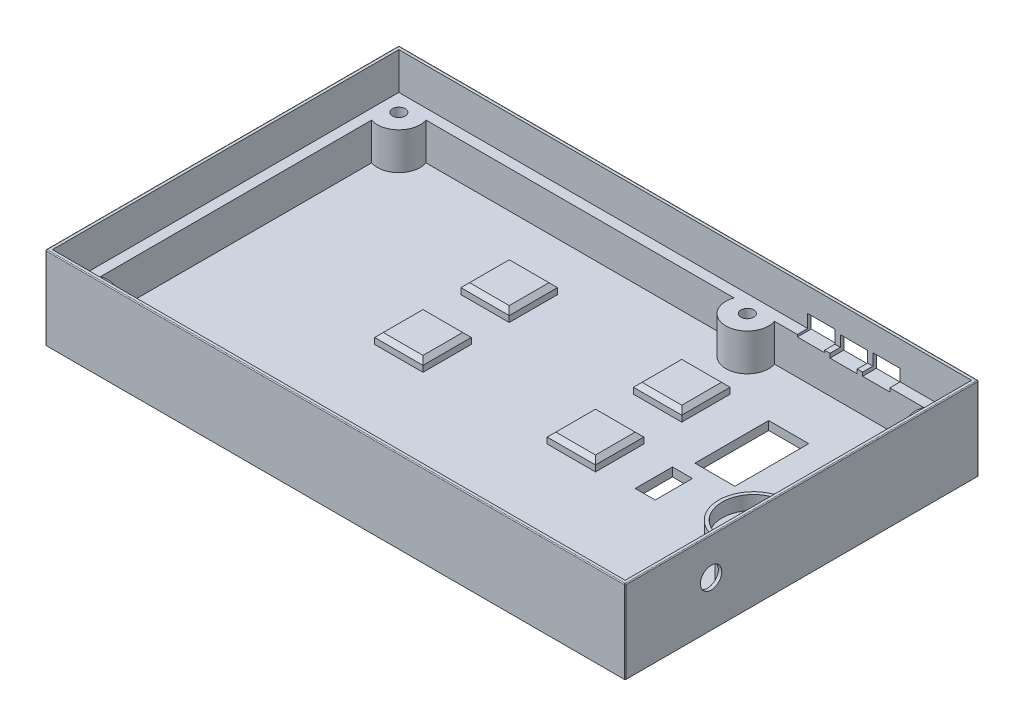
SolidWorks part; units mm, degrees
ref_plane "Front Plane" through (0, 0, 0) normal (0, 0, 1) x (1, 0, 0)
ref_plane "Top Plane" through (0, 0, 0) normal (0, 1, 0) x (1, 0, 0)
ref_plane "Right Plane" through (0, 0, 0) normal (1, 0, 0) x (0, 0, -1)
sketch "BaseSketch1" plane through (0, 0, 0) normal (0, 1, 0) x (1, 0, 0)
  line L1 (0, 0) -> (168, 0)
  line L2 (0, 0) -> (0, 102.4)
  line L3 (0, 102.4) -> (168, 102.4)
  line L4 (168, 0) -> (168, 102.4)
  line L5 (126.2, 83.4) -> (137.8, 83.4)
  line L6 (126.2, 83.4) -> (126.2, 62)
  line L7 (126.2, 62) -> (137.8, 62)
  line L8 (137.8, 83.4) -> (137.8, 62)
  line L9 (123.9, 47) -> (129.7, 47)
  line L10 (123.9, 47) -> (123.9, 57.8)
  line L11 (123.9, 57.8) -> (129.7, 57.8)
  line L12 (129.7, 47) -> (129.7, 57.8)
  circle A0 centre (57, 77.4) radius 2
  circle A1 centre (107, 77.4) radius 2
  circle A2 centre (57, 52.4) radius 2
  circle A3 centre (107, 52.4) radius 2
  circle A4 centre (6, 96.4) radius 1.85
  circle A5 centre (6, 6) radius 1.85
  circle A6 centre (162, 6) radius 1.85
  circle A7 centre (162, 96.4) radius 1.85
  circle A8 centre (107, 96.4) radius 1.85
  dimension "D16" = 3.7
  dimension "D7" = 4
  dimension "D1" = 102.4
  dimension "D2" = 168
  dimension "D3" = 50
  dimension "D4" = 25
  dimension "D6" = 25
  dimension "D8" = 21.4
  dimension "D9" = 11.6
  dimension "D10" = 40.4
  dimension "D12" = 5.8
  dimension "D13" = 10.8
  dimension "D15" = 55.4
  dimension "D17" = 6
  dimension "D18" = 6
  dimension "D19" = 6
  dimension "D20" = 6
  dimension "D5" = 57
  dimension "D11" = 41.8
  dimension "D14" = 44.1
  dimension "D21" = 107
extrude "BaseBoss-Extrude1" add sketch "BaseSketch1" along normal blind 2.5
sketch "Sketch2" plane through (0, 2.5, 0) normal (0, 1, 0) x (1, 0, 0)
  line L1 (0, 0) -> (168, 0)
  line L2 (0, 0) -> (0, 102.4)
  line L3 (0, 102.4) -> (168, 102.4)
  line L4 (168, 0) -> (168, 102.4)
  line L5 (4, 98.4) -> (164, 98.4)
  line L6 (4, 98.4) -> (4, 4)
  line L7 (4, 4) -> (164, 4)
  line L8 (164, 98.4) -> (164, 4)
  dimension "D1" = 4
  dimension "D2" = 4
  dimension "D3" = 4
  dimension "D4" = 4
extrude "WallBoss-Extrude2" add sketch "Sketch2" along normal blind 21.5
sketch "Sketch3" plane through (0, 2.5, 0) normal (0, 1, 0) x (1, 0, 0)
  line L1 (50, 84.4) -> (64, 84.4)
  line L2 (50, 84.4) -> (50, 70.4)
  line L3 (50, 70.4) -> (64, 70.4)
  line L4 (64, 84.4) -> (64, 70.4)
  line L5 (50, 84.4) -> (64, 70.4) construction
  line L6 (50, 70.4) -> (64, 84.4) construction
  line L7 (50, 59.4) -> (64, 59.4)
  line L8 (50, 59.4) -> (50, 45.4)
  line L9 (50, 45.4) -> (64, 45.4)
  line L10 (64, 59.4) -> (64, 45.4)
  line L11 (50, 59.4) -> (64, 45.4) construction
  line L12 (50, 45.4) -> (64, 59.4) construction
  line L13 (100, 84.4) -> (114, 84.4)
  line L14 (100, 84.4) -> (100, 70.4)
  line L15 (100, 70.4) -> (114, 70.4)
  line L16 (114, 84.4) -> (114, 70.4)
  line L17 (100, 84.4) -> (114, 70.4) construction
  line L18 (100, 70.4) -> (114, 84.4) construction
  line L19 (100, 59.4) -> (114, 59.4)
  line L20 (100, 59.4) -> (100, 45.4)
  line L21 (100, 45.4) -> (114, 45.4)
  line L22 (114, 59.4) -> (114, 45.4)
  line L23 (100, 59.4) -> (114, 45.4) construction
  line L24 (100, 45.4) -> (114, 59.4) construction
  point P0 (57, 77.4)
  point P6 (57, 52.4)
  point P12 (107, 77.4)
  point P18 (107, 52.4)
  dimension "D1" = 14
extrude "MountHoleBoss-Extrude3" add sketch "Sketch3" along normal blind 3
chamfer "MountHoleBossChamfer3" distance 1.25 angle 45 16 edges at (57, 5.5, -59.4) (107, 5.5, -59.4) (107, 5.5, -84.4) (57, 5.5, -84.4) (50, 5.5, -52.4) (100, 5.5, -52.4) (100, 5.5, -77.4) (50, 5.5, -77.4) (64, 5.5, -52.4) (114, 5.5, -52.4) (114, 5.5, -77.4) (64, 5.5, -77.4) (57, 5.5, -70.4) (57, 5.5, -45.4) (107, 5.5, -45.4) (107, 5.5, -70.4)
sketch "HDMI7MountHolesSketch8" plane through (0, 2.5, 0) normal (0, 1, 0) x (1, 0, 0)
  line L0 (164, 98.4) -> (4, 98.4) construction
  line L1 (4, 98.4) -> (4, 4) construction
  line L2 (4, 90.5243) -> (4, 98.4)
  line L3 (4, 98.4) -> (11.8757, 98.4)
  line L4 (164, 4) -> (164, 98.4) construction
  line L5 (4, 4) -> (164, 4) construction
  line L6 (4, 98.4) -> (4, 4) construction
  line L7 (4, 4) -> (164, 4) construction
  line L8 (156.1243, 98.4) -> (164, 98.4)
  line L9 (164, 98.4) -> (164, 90.5243)
  line L10 (156.1243, 4) -> (164, 4)
  line L11 (164, 4) -> (164, 11.8757)
  line L12 (11.8757, 4) -> (4, 4)
  line L13 (4, 4) -> (4, 11.8757)
  line L14 (101.1243, 98.4) -> (112.8757, 98.4)
  arc A0 (11.8757, 98.4) -> (4, 90.5243) centre (6, 96.4) cw
  circle A1 centre (6, 96.4) radius 1.85
  circle A2 centre (6, 96.4) radius 1.85 construction
  circle A3 centre (162, 96.4) radius 1.85
  circle A4 centre (162, 96.4) radius 1.85 construction
  arc A5 (164, 90.5243) -> (156.1243, 98.4) centre (162, 96.4) cw
  arc A6 (164, 11.8757) -> (156.1243, 4) centre (162, 6) ccw
  arc A7 (4, 11.8757) -> (11.8757, 4) centre (6, 6) cw
  circle A8 centre (162, 6) radius 1.85
  circle A9 centre (162, 6) radius 1.85 construction
  circle A10 centre (6, 6) radius 1.85
  circle A11 centre (6, 6) radius 1.85 construction
  arc A12 (101.1243, 98.4) -> (112.8757, 98.4) centre (107, 96.4) ccw
  circle A13 centre (107, 96.4) radius 1.85
  circle A14 centre (107, 96.4) radius 1.85 construction
extrude "HDMI7MountHolesBoss-Extrude4" add sketch "HDMI7MountHolesSketch8" along normal blind 10.75
sketch "DisplayButtonsSketch9" plane through (0, 0, -102.4) normal (0, 0, -1) x (-1, 0, 0)
  line L0 (-168, 24) -> (0, 24) construction
  line L1 (-146.3, 16.61) -> (-138.4, 16.61)
  line L2 (-146.3, 16.61) -> (-146.3, 12.21)
  line L3 (-146.3, 12.21) -> (-138.4, 12.21)
  line L4 (-138.4, 16.61) -> (-138.4, 12.21)
  line L5 (-136.85, 16.4439) -> (-128.95, 16.4439)
  line L6 (-136.85, 16.4439) -> (-136.85, 12.0439)
  line L7 (-136.85, 12.0439) -> (-128.95, 12.0439)
  line L8 (-128.95, 16.4439) -> (-128.95, 12.0439)
  line L9 (-127.4, 17.0239) -> (-119.5, 17.0239)
  line L10 (-127.4, 17.0239) -> (-127.4, 12.6239)
  line L11 (-127.4, 12.6239) -> (-119.5, 12.6239)
  line L12 (-119.5, 17.0239) -> (-119.5, 12.6239)
  line L13 (-168, 24) -> (-168, 0) construction
  dimension "D1" = 7.9
  dimension "D3" = 11.79
  dimension "D4" = 29.6
  dimension "D2" = 4.4
  dimension "D6" = 1.55
  dimension "D5" = 1.55
  dimension "D7" = 48.5
  dimension "D8" = 7.9
  dimension "D9" = 7.9
extrude "DisplayButtonsCut-Extrude1" cut sketch "DisplayButtonsSketch9" against normal up to next
sketch "AudioConnectorSketch10" plane through (168, 0, 0) normal (1, 0, 0) x (0, 0, -1)
  line L0 (0, 24) -> (102.4, 24) construction
  line L1 (0, 24) -> (0, 0) construction
  circle A0 centre (24.9, 13.2) radius 3.1
  dimension "D1" = 6.2
  dimension "D2" = 10.8
  dimension "D3" = 24.9
extrude "AudioConnectorCut-Extrude2" cut sketch "AudioConnectorSketch10" against normal up to next
sketch "M3BoreSketch11" plane through (0, 0, 0) normal (0, -1, 0) x (1, 0, 0)
  circle A0 centre (6, -6) radius 2.85
  circle A1 centre (162, -6) radius 2.85
  circle A2 centre (162, -96.4) radius 2.85
  circle A3 centre (6, -96.4) radius 2.85
  circle A4 centre (107, -96.4) radius 2.85
  dimension "D1" = 5.7
extrude "M3BoreCut-Extrude3" cut sketch "M3BoreSketch11" against normal blind 3
sketch "UpperThinWallSketch4" plane through (0, 24, 0) normal (0, 1, 0) x (1, 0, 0)
  line L1 (4, 98.4) -> (164, 98.4)
  line L2 (4, 98.4) -> (4, 4)
  line L3 (4, 4) -> (164, 4)
  line L4 (164, 98.4) -> (164, 4)
  line L6 (167, 1) -> (1, 1)
  line L7 (167, 1) -> (167, 101.4)
  line L8 (167, 101.4) -> (1, 101.4)
  line L9 (1, 1) -> (1, 101.4)
  dimension "D1" = 3
  dimension "D2" = 3
  dimension "D3" = 3
  dimension "D4" = 3
extrude "UpperThinWallCut-Extrude1" cut sketch "UpperThinWallSketch4" against normal blind 10.75
sketch "HDMI7AudioConnectorKnotchSketch5" plane through (0, 13.25, 0) normal (0, 1, 0) x (1, 0, 0)
  line L0 (164, 27.9996) -> (167, 27.9996) construction
  line L1 (164, 29.9996) -> (167, 29.9996)
  line L2 (164, 29.9996) -> (164, 19.8004)
  line L3 (164, 19.8004) -> (167, 19.8004)
  line L4 (167, 29.9996) -> (167, 19.8004)
  line L6 (167, 1) -> (167, 21.8004) construction
  line L7 (164, 11.8757) -> (164, 90.5243) construction
  line L8 (167, 21.8004) -> (164, 21.8004) construction
  dimension "D1" = 2
  dimension "D2" = 2
extrude "HDMI7AudioConnectorKnotchCut-Extrude2" cut sketch "HDMI7AudioConnectorKnotchSketch5" against normal blind 8.2
fillet "TopFillet1" radius 0.25 4 edges at (168, 24, -51.2) (84, 24, 0) (0, 24, -51.2) (84, 24, -102.4)
fillet "CornerFillet2" radius 0.25 8 edges at (0.0732, 23.9268, -0.0732) (0.0732, 23.9268, -102.3268) (167.9268, 23.9268, -0.0732) (0, 11.875, 0) (0, 11.875, -102.4) (168, 11.875, 0) (167.9268, 23.9268, -102.3268) (168, 11.875, -102.4)
sketch "SpeakerHoleSketch4" plane through (0, 2.5, 0) normal (0, 1, 0) x (1, 0, 0)
  line L0 (0.25, 102.4) -> (167.75, 102.4) construction
  line L1 (168, 102.15) -> (168, 0.25) construction
  circle A0 centre (153, 52.2) radius 6.75
  dimension "D1" = 13.5
  dimension "D2" = 50.2
  dimension "D3" = 15
extrude "SpeaerHoleCut-Extrude1" cut sketch "SpeakerHoleSketch4" against normal through all
sketch "SpeakerHolderSketch5" plane through (0, 2.5, 0) normal (0, 1, 0) x (1, 0, 0)
  line L2 (50, 59.4) -> (50, 45.4) construction
  line L3 (50, 45.4) -> (64, 45.4) construction
  circle A0 centre (153, 52.2) radius 9.1
  circle A1 centre (153, 52.2) radius 10.1
  dimension "D1" = 18.2
  dimension "D2" = 20.2
extrude "SpeakerHolderBoss-Extrude1" add sketch "SpeakerHolderSketch5" along normal blind 4
equation "\"HDMI7CaseWidth\"= 100mm + .4mm'Spec Add .4mm as width was slightly to tight"
equation "\"D1@BaseSketch1\" = \"HDMI7CaseWidth\" + \"HDMI7OuterCaseWallThickness\" * 2"
equation "\"HDMI7CaseLength\"= 165mm + 1mm'Spec Add 1mm as length did not fit"
equation "\"HDMI7CaseHeight\"= 24mm"
equation "\"HDMI7Height\"= 10.75mm'Spec"
equation "\"HDMI7MountingHoleOffset\"= 5mm'Spec"
equation "\"M3ScrewDiameter\"= 3mm + .5'Spec Add .5mm for easy screw insert"
equation "\"D2@BaseSketch1\"= \"HDMI7CaseLength\" + \"HDMI7OuterCaseWallThickness\" * 2"
equation "\"HDMI7BaseThickness\"= 2.5mm"
equation "\"HDMIMountHoleXDistance\"=50"
equation "\"D3@BaseSketch1\"=\"HDMIMountHoleXDistance\""
equation "\"HDMIMountHoleYDistance\"=25"
equation "\"D10@BaseSketch1\"=\"HDMI7HDMIConnectorDistanceFromTop\" + \"HDMI7OuterCaseWallThickness\" + \"HDMI7SpaceAroundAConnector\""
equation "\"D6@BaseSketch1\" = \"HDMI7MountingBracketOffsetFromTop\" + \"HDMI7OuterCaseWallThickness\""
equation "\"D15@BaseSketch1\"=\"HDMI7USBCConnectorDistanceFromTop\" + \"HDMI7OuterCaseWallThickness\" + \"HDMI7SpaceAroundAConnector\"*2"
equation "\"D1@BaseBoss-Extrude1\" = \"HDMI7BaseThickness\""
equation "\"D1@Sketch2\"=\"HDMI7OuterCaseWallThickness\" + \"HDMI7InnerCaseWallThickness\""
equation "\"D2@Sketch2\"=\"HDMI7OuterCaseWallThickness\" + \"HDMI7InnerCaseWallThickness\""
equation "\"D3@Sketch2\"=\"HDMI7OuterCaseWallThickness\" +\"HDMI7InnerCaseWallThickness\""
equation "\"D4@Sketch2\"=\"HDMI7OuterCaseWallThickness\" + \"HDMI7InnerCaseWallThickness\""
equation "\"D1@WallBoss-Extrude2\" = \"HDMI7CaseHeight\" - \"HDMI7BaseThickness\""
equation "\"D1@Sketch3\"=\"M3ScrewDiameter\"*4"
equation "\"D1@MountHoleBoss-Extrude3\"=\"M3ButtonHeadLength\""
equation "\"D16@BaseSketch1\"=\"M3ScrewDiameter\" +.2"
equation "\"D18@BaseSketch1\"=\"HDMI7MountingHoleOffset\" + \"HDMI7OuterCaseWallThickness\""
equation "\"D17@BaseSketch1\"=\"HDMI7MountingHoleOffset\"+\"HDMI7OuterCaseWallThickness\""
equation "\"D19@BaseSketch1\"=\"HDMI7MountingHoleOffset\"+\"HDMI7OuterCaseWallThickness\""
equation "\"D20@BaseSketch1\"=\"HDMI7MountingHoleOffset\"+\"HDMI7OuterCaseWallThickness\""
equation "\"D1@HDMI7MountHolesBoss-Extrude4\"=\"HDMI7CaseHeight\" - \"HDMI7Height\" - \"HDMI7BaseThickness\""
equation "\"D5@BaseSketch1\" = \"HDMI7MountingBracketOffsetFromEdge\" + \"HDMI7OuterCaseWallThickness\""
equation "\"D4@DisplayButtonsSketch9\"=\"HDMI7DisplayButtonDistanceFromNearestEdge\" + \"HDMI7OuterCaseWallThickness\" + \"HDMI7SpaceAroundAConnector\""
equation "\"D2@AudioConnectorSketch10\"= \"HDMI7AudioConnectorDistanceFromTop\" - \"HDMI7AudioConnectorHoleDiameter\" / 2"
equation "\"D3@AudioConnectorSketch10\"= \"HDMI7AudioConnectorDistanceFromNearestEdge\" + \"HDMI7OuterCaseWallThickness\" - \"HDMI7AudioConnectorHoleDiameter\" / 2"
equation "\"M3ButtonHeadDiameter\"= 5.5mm'Spec"
equation "\"M3ButtonHeadLength\"= 3mm'Spec"
equation "\"D1@M3BoreSketch11\"=\"M3ButtonHeadDiameter\" + .2mm"
equation "\"D1@M3BoreCut-Extrude3\"=\"M3ButtonHeadLength\""
equation "\"HDMI7InnerCaseWallThickness\"= 3mm"
equation "\"HDMI7OuterCaseWallThickness\"= 1mm"
equation "\"D1@UpperThinWallSketch4\" = \"HDMI7InnerCaseWallThickness\""
equation "\"D2@UpperThinWallSketch4\" = \"HDMI7InnerCaseWallThickness\""
equation "\"D3@UpperThinWallSketch4\" = \"HDMI7InnerCaseWallThickness\""
equation "\"D4@UpperThinWallSketch4\" = \"HDMI7InnerCaseWallThickness\""
equation "\"D1@UpperThinWallCut-Extrude1\" = \"HDMI7Height\""
equation "\"HDMI7AudioConnectorHoleDiameter\"= 6mm + \"HDMI7SpaceAroundAConnector\" * 2"
equation "\"D1@AudioConnectorSketch10\"=\"HDMI7AudioConnectorHoleDiameter\""
equation "\"HDMI7AudioConnectorDistanceFromNearestEdge\"= 27mm"
equation "\"HDMI7AudioConnectorDistanceFromTop\"= 13.8mm + \"HDMI7SpaceAroundAConnector\""
equation "\"D1@HDMI7AudioConnectorKnotchCut-Extrude2\"=\"HDMI7AudioConnectorHoleDiameter\" + 2mm"
equation "\"HDMI7DisplayButtonDistanceFromTop\"=11.69"
equation "\"D3@DisplayButtonsSketch9\"=\"HDMI7DisplayButtonDistanceFromTop\" + \"HDMI7SpaceAroundAConnector\""
equation "\"HDMI7DisplayButtonHeight\"= 4.2mm"
equation "\"D2@DisplayButtonsSketch9\"=\"HDMI7DisplayButtonHeight\" + \"HDMI7SpaceAroundAConnector\"*2"
equation "\"HDMI7DisplayButtonWidth\"= 7.7mm"
equation "\"D1@DisplayButtonsSketch9\"=\"HDMI7DisplayButtonWidth\" + \"HDMI7SpaceAroundAConnector\" * 2"
equation "\"HDMI7DisplayButtonDistanceFromNearestEdge\"= 28.5mm"
equation "\"HDMI7DisplayButtonOffsetBetweenEach\"=1.75"
equation "\"D6@DisplayButtonsSketch9\"=\"HDMI7DisplayButtonOffsetBetweenEach\" - \"HDMI7SpaceAroundAConnector\"*2"
equation "\"D5@DisplayButtonsSketch9\"=\"HDMI7DisplayButtonOffsetBetweenEach\" - \"HDMI7SpaceAroundAConnector\"*2"
equation "\"HDMI7HDMIConnectorLength\"= 21.2mm'Measured"
equation "\"D8@BaseSketch1\"=\"HDMI7HDMIConnectorLength\" + \"HDMI7SpaceAroundAConnector\"*2"
equation "\"HDMI7HDMIConnectorWidth\"= 11.5mm'Measured"
equation "\"D9@BaseSketch1\"=\"HDMI7HDMIConnectorWidth\" + \"HDMI7SpaceAroundAConnector\""
equation "\"HDMI7USBCConnectorLength\"= 10.7mm'Measured"
equation "\"D13@BaseSketch1\"=\"HDMI7USBCConnectorLength\" + \"HDMI7SpaceAroundAConnector\""
equation "\"HDMI7USBCConnectorWidth\"= 5.7mm'Measured"
equation "\"D12@BaseSketch1\"=\"HDMI7USBCConnectorWidth\" + \"HDMI7SpaceAroundAConnector\""
equation "\"HDMI7HDMIConnectorDistanceFromNearestSide\"= 38.7mm"
equation "\"HDMI7USBCConnectorDistanceFromNearestSide\"= 41mm"
equation "\"D11@BaseSketch1\"=\"HDMI7HDMIConnectorDistanceFromNearestSide\" + \"HDMI7InnerCaseWallThickness\" + \"HDMI7SpaceAroundAConnector\""
equation "\"D14@BaseSketch1\"=\"HDMI7USBCConnectorDistanceFromNearestSide\" +\"HDMI7InnerCaseWallThickness\" + \"HDMI7SpaceAroundAConnector\""
equation "\"HDMI7USBCConnectorDistanceFromTop\"= 54.2mm"
equation "\"HDMI7HDMIConnectorDistanceFromTop\"= 39.3mm"
equation "\"HDMI7MountingBracketOffsetFromEdge\"= 56mm"
equation "\"HDMI7MountingBracketOffsetFromTop\"= 24mm"
equation "\"HDMI7SpaceAroundAConnector\"= .1mm"
equation "\"D7@BaseSketch1\"= \"M3HeatInsertHoleDiameter\""
equation "\"D8@DisplayButtonsSketch9\"=\"HDMI7DisplayButtonWidth\" + \"HDMI7SpaceAroundAConnector\"*2"
equation "\"D9@DisplayButtonsSketch9\"=\"HDMI7DisplayButtonWidth\" + \"HDMI7SpaceAroundAConnector\"*2"
equation "\"HDMI7MidMouningHoleOffset\"= 107'Spec is 106.55 but not enough"
equation "\"M3HeatInsertHoleDiameter\"= 4mm'Spec"
equation "\"SpeakerHoleDiameter\"= 13.5mm"
equation "\"D2@SpeakerHoleSketch4\" = \"HDMI7CaseWidth\" / 2"
equation "\"SpeakerDistanceFromNearestEdge\"= 15mm"
equation "\"D3@SpeakerHoleSketch4\" = \"SpeakerDistanceFromNearestEdge\""
equation "\"SpeakerDiameter\"= 18.2mm'Spec Add .2mm for Filament expansion"
equation "\"D1@SpeakerHolderSketch5\"=\"SpeakerDiameter\""
equation "\"D2@SpeakerHolderSketch5\"=\"SpeakerDiameter\" + 2mm"
equation "\"SpeakerDepth\"=4"
equation "\"D1@SpeakerHolderBoss-Extrude1\"=\"SpeakerDepth\""
equation "\"D21@BaseSketch1\"=\"HDMI7MidMouningHoleOffset\""
